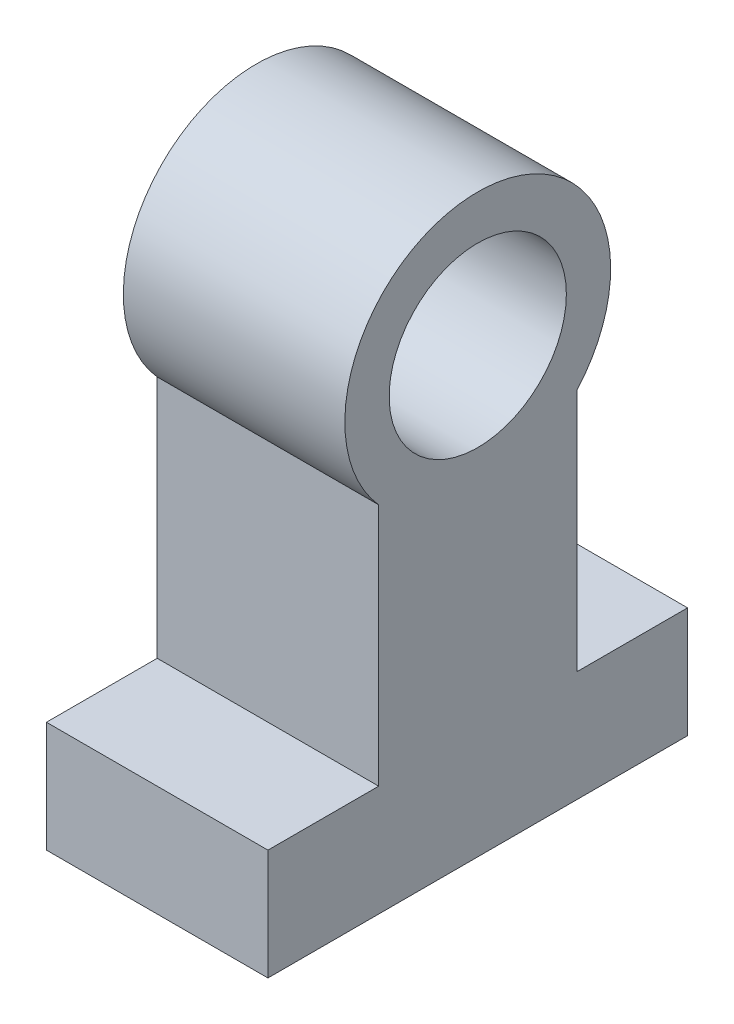
SolidWorks part; units mm, degrees
material "Pure Lead"
ref_plane "Front Plane" through (0, 0, 0) normal (0, 0, 1) x (1, 0, 0)
ref_plane "Top Plane" through (0, 0, 0) normal (0, 1, 0) x (1, 0, 0)
ref_plane "Right Plane" through (0, 0, 0) normal (1, 0, 0) x (0, 0, -1)
sketch "LinkFrame" plane through (0, 0, 0) normal (1, 0, 0) x (0, 0, -1)
  line L5 (306.1892, -256.0436) -> (306.1892, -366.0436)
  line L7 (216.7465, -256.0436) -> (216.7465, -366.0436)
  line L8 (261.4679, -216.0436) -> (261.4679, -416.0436) construction
  line L9 (166.7465, -366.0436) -> (216.7465, -366.0436)
  line L10 (166.7465, -366.0436) -> (166.7465, -416.0436)
  line L11 (166.7465, -416.0436) -> (356.1892, -416.0436)
  line L12 (356.1892, -366.0436) -> (356.1892, -416.0436)
  line L13 (306.1892, -366.0436) -> (356.1892, -366.0436)
  line L14 (221.5147, -214.1094) -> (261.4679, -216.0436) construction
  circle A6 centre (261.4679, -216.0436) radius 40
  arc A7 (306.1892, -256.0436) -> (216.7465, -256.0436) centre (261.4679, -216.0436) ccw
  dimension "D6" = 80
  dimension "D2" = 120
  dimension "D10" = 50
  dimension "D9" = 50
  dimension "D12" = 50
  dimension "D11" = 200
extrude "Boss-Extrude1" add sketch "LinkFrame" along normal blind 100
equation "\"LinkLength\"= 80cm"
equation "\"D6@LinkFrame\"=\"HoleMountDiameter@PrintingPress.Assembly\""
equation "\"D1@Boss-Extrude1\"=\"RivetLength@PrintingPress.Assembly\""
equation "\"D10@LinkFrame\"=0.5*\"RivetLength@PrintingPress.Assembly\""
equation "\"D9@LinkFrame\"=0.5*\"RivetLength@PrintingPress.Assembly\""
equation "\"D12@LinkFrame\"=0.5*\"RivetLength@PrintingPress.Assembly\""
equation "\"D2@LinkFrame\"=1.5*\"HoleMountDiameter@PrintingPress.Assembly\""
